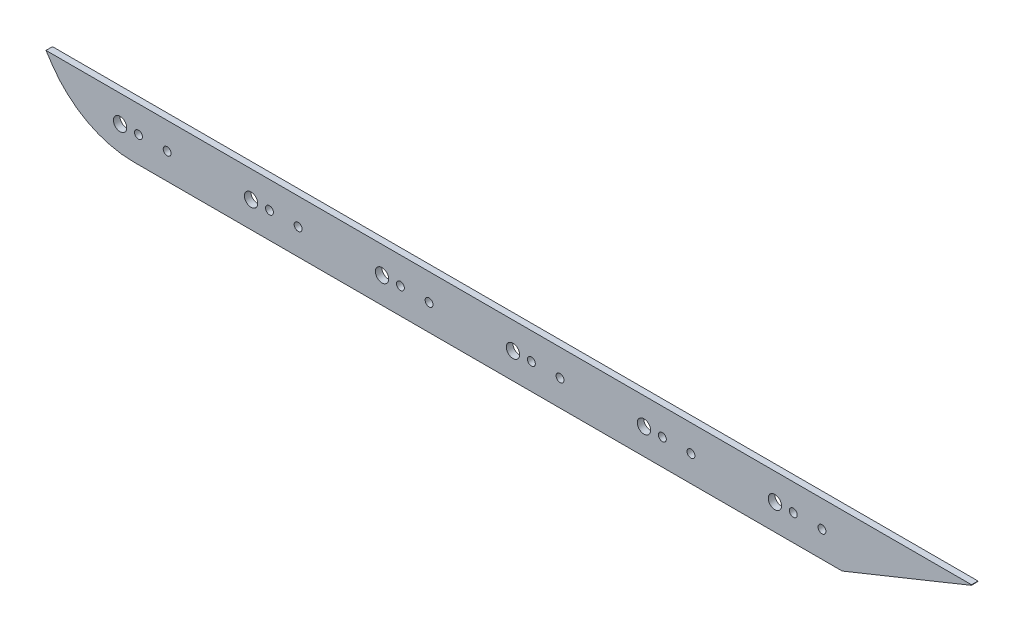
SolidWorks part; units mm, degrees
material "5052-H34"
ref_plane "Front Plane" through (0, 0, 0) normal (0, 0, 1) x (1, 0, 0)
ref_plane "Top Plane" through (0, 0, 0) normal (0, 1, 0) x (1, 0, 0)
ref_plane "Right Plane" through (0, 0, 0) normal (1, 0, 0) x (0, 0, -1)
sketch "Sketch1" plane through (0, 0, 0) normal (0, 0, 1) x (1, 0, 0)
  line L3 (428.1206, 28.9396) -> (0.5404, 28.9396)
  line L6 (-98.8794, 3.851) -> (-31.8794, -96.649)
  line L7 (428.1206, 28.9396) -> (403.1206, -71.149)
  line L9 (403.1206, -71.149) -> (366, -96.649)
  line L10 (-31.8794, -96.649) -> (366, -96.649)
  line L11 (0.5404, 28.9396) -> (-115.6052, 28.9396)
  line L12 (-98.8794, 3.851) -> (-115.6052, 28.9396)
  line L13 (-49.0861, -70.839) -> (403.198, -70.839)
  circle A0 centre (-12.8794, -83.899) radius 3.25
  circle A1 centre (51.1206, -83.899) radius 3.25
  circle A2 centre (115.1206, -83.899) radius 3.25
  circle A3 centre (179.1206, -83.899) radius 3.25
  circle A4 centre (243.1206, -83.899) radius 3.25
  circle A5 centre (307.1206, -83.899) radius 3.25
  point P0 (-48.8794, -71.149)
  point P2 (-31.8794, -96.649)
  point P8 (48, -83.899)
  point P9 (403.1206, -71.149)
  point P23 (-49.0861, -70.839)
  point P26 (403.198, -70.839)
  dimension "D2" = 64
  dimension "D4" = 64
  dimension "D16" = 6.5
  dimension "D1" = 25.5
  dimension "D3" = 75
  dimension "D5" = 25
  dimension "D6" = 96
  dimension "D7" = 527
  dimension "D8" = 180
  dimension "D9" = 64
  dimension "D10" = 64
  dimension "D11" = 64
  dimension "D12" = 123.69
  dimension "D13" = 12.75
  dimension "D14" = 25.81
  dimension "D15" = 25.81
extrude "Boss-Extrude1" add sketch "Sketch1" along normal blind 3.175 contours L3 L11 L12 L6 L10 L9 L7
extrude "Cut-Extrude1" cut sketch "Sketch1<4>" along normal through all contours A0 | A1 | A2 | A3 | A4 | A5 region at (-12.8794, -83.899, 0)
sketch "Sketch1<4>" plane through (0, 0, 0) normal (0, 0, 1) x (1, 0, 0) same geometry as "Sketch1"
sketch "Sketch2" plane through (0, 0, 0) normal (0, 0, -1) x (-1, 0, 0)
  circle A0 centre (-275.1206, -83.899) radius 6.5
  circle A2 centre (-233.5603, -132.5687) radius 6.5
  circle A3 centre (-192, -83.899) radius 6.5
  circle A4 centre (-128, -83.899) radius 6.5
  circle A5 centre (-64, -83.899) radius 6.5
  circle A6 centre (0, -83.899) radius 6.5
  dimension "D2" = 0
  dimension "D3" = 64
  dimension "D4" = 64
  dimension "D5" = 64
  dimension "D6" = 64
  dimension "D7" = 64
  dimension "D1" = 32
sketch "Sketch5" plane through (0, 0, 0) normal (0, 0, -1) x (-1, 0, 0)
  line L0 (48.8794, -71.149) -> (-14.2353, -96.649)
  line L1 (31.8794, -96.649) -> (-366, -96.649) construction
  line L2 (-14.2353, -96.649) -> (31.8794, -96.649)
  line L3 (31.8794, -96.649) -> (48.8794, -71.149)
  line L6 (-366, -96.649) -> (-403.1206, -71.149)
  line L7 (-403.1206, -71.149) -> (-352, -71.149)
  line L9 (-352, -71.149) -> (-326.5, -96.649)
  line L11 (-366, -96.649) -> (-326.5, -96.649)
  dimension "D1" = 22
  dimension "D2" = 45
extrude "Cut-Extrude2" [suppressed] cut sketch "Sketch5" against normal up to next
sketch "Sketch6" plane through (0, 0, 3.175) normal (0, 0, 1) x (1, 0, 0)
  line L0 (-48.8794, -71.149) -> (14.2353, -96.649)
  line L1 (-31.8794, -96.649) -> (366, -96.649) construction
  line L2 (14.2353, -96.649) -> (-31.8794, -96.649)
  line L3 (-31.8794, -96.649) -> (-48.8794, -71.149)
  dimension "D1" = 158
fillet "Fillet1" radius 48 1 edges at (-31.8794, -96.649, 1.5875)
sketch "Sketch7" plane through (0, 0, 3.175) normal (0, 0, 1) x (1, 0, 0)
  line L0 (403.1206, -71.149) -> (340.0059, -96.649)
  line L1 (-31.8794, -96.649) -> (366, -96.649) construction
  line L2 (340.0059, -96.649) -> (366, -96.649)
  line L3 (366, -96.649) -> (403.1206, -71.149)
  dimension "D1" = 22
extrude "Cut-Extrude3" cut sketch "Sketch7" against normal blind 10
sketch "Sketch9" plane through (0, 0, 0) normal (0, 0, -1) x (-1, 0, 0)
  line L0 (-403.1206, -71.149) -> (48.8794, -71.149)
  line L1 (48.8794, -71.149) -> (48.8794, -114.9143)
  line L2 (48.8794, -114.9143) -> (-403.1206, -114.9143)
  line L3 (-403.1206, -114.9143) -> (-403.1206, -71.149)
extrude "Cut-Extrude4" [suppressed] cut sketch "Sketch9" against normal blind 10
sketch "Sketch10" plane through (0, 0, 3.175) normal (0, 0, 1) x (1, 0, 0)
  line L0 (-49.0861, -70.839) -> (403.198, -70.839) construction
  line L1 (-49.0861, -70.839) -> (403.198, -70.839)
  line L2 (-49.0861, -70.839) -> (-115.6052, 28.9396)
  line L3 (-115.6052, 28.9396) -> (428.1206, 28.9396)
  line L4 (428.1206, 28.9396) -> (403.198, -70.839)
extrude "Cut-Extrude5" cut sketch "Sketch10" against normal blind 10
sketch "Sketch11" plane through (0, 0, 3.175) normal (0, 0, 1) x (1, 0, 0)
  line L0 (-12.8794, -83.899) -> (1.9194, -83.899) construction
  circle A0 centre (-3.8794, -83.899) radius 1.925
  circle A1 centre (10.1206, -83.899) radius 1.925
  circle A4 centre (60.1206, -83.899) radius 1.925
  circle A5 centre (74.1206, -83.899) radius 1.925
  circle A6 centre (124.1206, -83.899) radius 1.925
  circle A7 centre (138.1206, -83.899) radius 1.925
  circle A8 centre (188.1206, -83.899) radius 1.925
  circle A9 centre (202.1206, -83.899) radius 1.925
  circle A10 centre (252.1206, -83.899) radius 1.925
  circle A11 centre (266.1206, -83.899) radius 1.925
  circle A12 centre (316.1206, -83.899) radius 1.925
  circle A13 centre (330.1206, -83.899) radius 1.925
  dimension "D3" = 3.85
  dimension "D1" = 9
  dimension "D2" = 14
  dimension "D4" = 9
  dimension "D5" = 14
  dimension "D6" = 9
  dimension "D7" = 14
  dimension "D8" = 9
  dimension "D9" = 14
  dimension "D10" = 9
  dimension "D11" = 14
  dimension "D12" = 9
  dimension "D13" = 14
extrude "Cut-Extrude6" cut sketch "Sketch11" against normal blind 10
